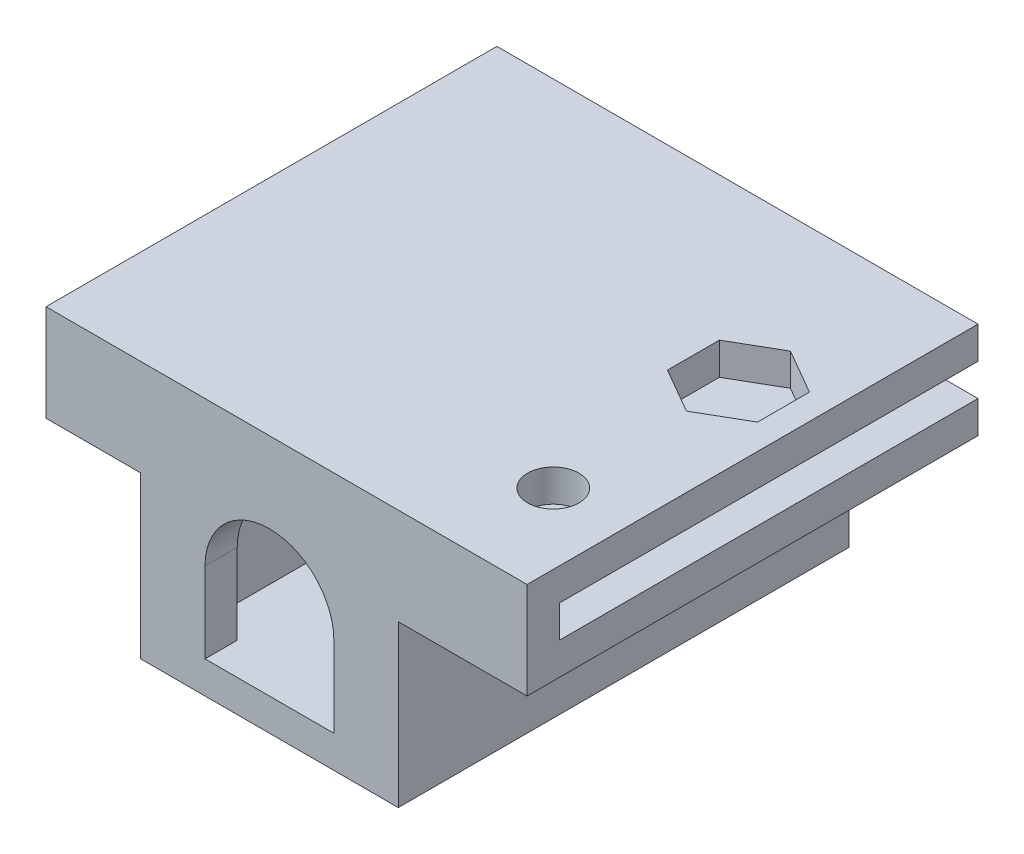
SolidWorks part; units mm, degrees
ref_plane "前视基准面" through (0, 0, 0) normal (0, 0, 1) x (1, 0, 0)
ref_plane "上视基准面" through (0, 0, 0) normal (0, 1, 0) x (1, 0, 0)
ref_plane "右视基准面" through (0, 0, 0) normal (1, 0, 0) x (0, 0, -1)
sketch "草图1" plane through (0, 0, 0) normal (0, 0, 1) x (1, 0, 0)
  line L0 (8, 3) -> (16, 3)
  line L1 (8, -7) -> (-8, -7)
  line L2 (8, -7) -> (8, 3)
  line L3 (8, 5) -> (-8, 5)
  line L4 (6, -4) -> (6, 4)
  line L5 (5, 5) -> (-5, 5)
  line L6 (-6, 4) -> (-6, -4)
  line L7 (-5, -5) -> (5, -5)
  line L8 (6, -4) -> (6, 4)
  line L9 (5, 5) -> (-5, 5)
  line L10 (-6, 4) -> (-6, -4)
  line L11 (-5, -5) -> (5, -5)
  line L12 (88.125, 7) -> (-11.875, 7)
  line L13 (-11.875, 7) -> (-11.875, 5)
  line L14 (-11.875, 5) -> (88.125, 5)
  line L15 (88.125, 5) -> (88.125, 7)
  line L16 (88.125, 7) -> (-11.875, 7)
  line L17 (-11.875, 7) -> (-11.875, 5)
  line L18 (-11.875, 5) -> (88.125, 5)
  line L19 (88.125, 5) -> (88.125, 7)
  line L20 (-8, -7) -> (-8, 3)
  line L21 (-13.875, 3) -> (-8, 3)
  line L22 (-13.875, 3) -> (-13.875, 9)
  line L23 (-13.875, 9) -> (16, 9)
  line L24 (16, 3) -> (16, 9)
  line L26 (4, 0) -> (4, -5)
  line L27 (4, -5) -> (-4, -5)
  line L28 (-4, 0) -> (-4, -5)
  arc A0 (4, 0) -> (-4, 0) centre (0, 0) ccw
  arc A4 (6, 4) -> (5, 5) centre (5, 4) ccw
  arc A5 (-5, 5) -> (-6, 4) centre (-5, 4) ccw
  arc A6 (-6, -4) -> (-5, -5) centre (-5, -4) ccw
  arc A7 (5, -5) -> (6, -4) centre (5, -4) ccw
  arc A8 (6, 4) -> (5, 5) centre (5, 4) ccw
  arc A9 (-5, 5) -> (-6, 4) centre (-5, 4) ccw
  arc A10 (-6, -4) -> (-5, -5) centre (-5, -4) ccw
  arc A11 (5, -5) -> (6, -4) centre (5, -4) ccw
  dimension "D5" = 2
  dimension "D6" = 2
  dimension "D1" = 0
  dimension "D2" = 0
extrude "凸台-拉伸1" add sketch "草图1" along normal blind 2 contours A11 L11 A10 L10 A9 L3 L18 L17 L16 L24 L23 L22 L21 L20 L1 L2 L0 A8 L8 | L18 L24 L16 L17 L3 | L11 A11 L8 A8 L3 A9 L10 A10 L28 A0 L26 region at (7.6611, -2, 0) region at (2.0625, 6, 0) region at (5.5967, 4.5967, 0)
sketch "草图2" plane through (0, 0, 0) normal (0, 0, -1) x (-1, 0, 0)
  line L1 (6, -5) -> (-6, -5)
  line L2 (6, -5) -> (6, 5)
  line L3 (6, 5) -> (-6, 5)
  line L4 (-6, 4) -> (-6, -4)
  line L5 (5, 5) -> (-5, 5)
  line L6 (6, -4) -> (6, 4)
  line L7 (-5, -5) -> (5, -5)
  line L8 (-6, 4) -> (-6, -4)
  line L9 (5, 5) -> (-5, 5)
  line L10 (6, -4) -> (6, 4)
  line L11 (-5, -5) -> (5, -5)
  line L12 (-16, 9) -> (-16, 3)
  line L13 (-16, 3) -> (-8, 3)
  line L14 (-8, 3) -> (-8, -7)
  line L15 (-8, -7) -> (8, -7)
  line L16 (8, -7) -> (8, 3)
  line L17 (8, 3) -> (13.875, 3)
  line L18 (13.875, 3) -> (13.875, 9)
  line L19 (13.875, 9) -> (-16, 9)
  line L23 (11.875, 7) -> (-88.125, 7)
  line L24 (-16, 9) -> (-16, 3)
  line L25 (-16, 3) -> (-8, 3)
  line L26 (-8, 3) -> (-8, -7)
  line L27 (-8, -7) -> (8, -7)
  line L28 (8, -7) -> (8, 3)
  line L29 (8, 3) -> (13.875, 3)
  line L30 (13.875, 3) -> (13.875, 9)
  line L31 (13.875, 9) -> (-16, 9)
  line L36 (-6, -5) -> (-6, 5)
  line L37 (11.875, 5) -> (11.875, 7)
  line L38 (-88.125, 5) -> (11.875, 5)
  line L39 (-88.125, 7) -> (-88.125, 5)
  line L40 (11.875, 7) -> (-88.125, 7)
  line L41 (11.875, 5) -> (11.875, 7)
  line L42 (-88.125, 5) -> (11.875, 5)
  line L43 (-88.125, 7) -> (-88.125, 5)
  arc A4 (-5, 5) -> (-6, 4) centre (-5, 4) ccw
  arc A5 (6, 4) -> (5, 5) centre (5, 4) ccw
  arc A6 (5, -5) -> (6, -4) centre (5, -4) ccw
  arc A7 (-6, -4) -> (-5, -5) centre (-5, -4) ccw
  arc A8 (-5, 5) -> (-6, 4) centre (-5, 4) ccw
  arc A9 (6, 4) -> (5, 5) centre (5, 4) ccw
  arc A10 (5, -5) -> (6, -4) centre (5, -4) ccw
  arc A11 (-6, -4) -> (-5, -5) centre (-5, -4) ccw
  line M21 (4, -5) -> (-4, -5)
  line M25 (-16, 9) -> (-16, 3)
  line M26 (-16, 3) -> (-8, 3)
  line M27 (-8, 3) -> (-8, -7)
  line M28 (-8, -7) -> (8, -7)
  line M29 (8, -7) -> (8, 3)
  line M30 (8, 3) -> (13.875, 3)
  line M31 (13.875, 3) -> (13.875, 9)
  line M32 (13.875, 9) -> (-16, 9)
  line M33 (-16, 9) -> (-16, 3)
  dimension "D1" = 0
  dimension "D2" = 0
  dimension "D3" = 0
extrude "凸台-拉伸2" add sketch "草图2" along normal offset from surface (26 mm away) 2 contours L1 L36 L8 L2 M25 M26 M27 M28 M29 M30 M31 M32 M33 M21 region at (-6.3389, -4.5, 0) offset beyond the face yes
sketch "草图3" plane through (0, 0, -26) normal (0, 0, -1) x (-1, 0, 0)
  line L1 (6, -5) -> (-6, -5)
  line L2 (6, -5) -> (6, -4)
  line L3 (6, -4) -> (-6, -4)
  line L4 (-6, -5) -> (-6, -4)
  line L20 (-16, 5) -> (-16, 3)
  line L21 (-16, 3) -> (-8, 3)
  line L22 (-8, 3) -> (-8, -7)
  line L23 (-8, -7) -> (8, -7)
  line L24 (8, -7) -> (8, 3)
  line L25 (8, 3) -> (13.875, 3)
  line L26 (13.875, 3) -> (13.875, 9)
  line L27 (13.875, 9) -> (-16, 9)
  line L28 (6, 5) -> (6, -5)
  line L29 (6, 5) -> (6, -5)
  line L30 (6, -5) -> (-6, -5)
  line L31 (6, -5) -> (-6, -5)
  line L36 (-16, 5) -> (-16, 3)
  line L37 (-16, 3) -> (-8, 3)
  line L38 (-8, 3) -> (-8, -7)
  line L39 (-8, -7) -> (8, -7)
  line L40 (8, -7) -> (8, 3)
  line L41 (8, 3) -> (13.875, 3)
  line L42 (13.875, 3) -> (13.875, 9)
  line L43 (13.875, 9) -> (-16, 9)
  line L48 (-6, -5) -> (-6, 5)
  line L49 (-6, -5) -> (-6, 5)
  line L50 (-6, 5) -> (-16, 5)
  line L51 (-6, 5) -> (-16, 5)
  line L52 (-16, 9) -> (-16, 7)
  line L53 (-16, 9) -> (-16, 7)
  line L54 (-16, 7) -> (11.875, 7)
  line L55 (-16, 7) -> (11.875, 7)
  line L56 (11.875, 7) -> (11.875, 5)
  line L57 (11.875, 7) -> (11.875, 5)
  line L58 (11.875, 5) -> (6, 5)
  line L59 (11.875, 5) -> (6, 5)
  line M19 (6, 5) -> (6, -5)
  line M20 (6, -5) -> (-6, -5)
  line M21 (-6, -5) -> (-6, 5)
  dimension "D2" = 1
  dimension "D1" = 0
extrude "凸台-拉伸3" add sketch "草图3" against normal blind 1.6 contours L3 M19 M21 M20 region at (0, -4.5, -26)
sketch "草图4" plane through (0, 9, 0) normal (0, 1, 0) x (1, 0, 0)
  line L0 (13.92, 16.825) -> (9.33, 14.175) construction
  line L2 (11.625, 12.2726) -> (14.42, 13.8863)
  line L3 (14.42, 13.8863) -> (14.42, 17.1137)
  line L4 (16, -2) -> (16, 26)
  line L5 (16, 26) -> (-13.875, 26)
  line L6 (-13.875, 26) -> (-13.875, -2)
  line L7 (-13.875, -2) -> (16, -2)
  line L8 (16, -2) -> (16, 26)
  line L9 (16, 26) -> (-13.875, 26)
  line L10 (-13.875, 26) -> (-13.875, -2)
  line L11 (-13.875, -2) -> (16, -2)
  line L12 (14.42, 17.1137) -> (11.625, 18.7274)
  line L13 (11.625, 18.7274) -> (8.83, 17.1137)
  line L14 (11.625, 18.15) -> (9.33, 16.825)
  line L15 (9.33, 16.825) -> (9.33, 14.175)
  line L16 (9.33, 14.175) -> (11.625, 12.85)
  line L17 (11.625, 12.85) -> (13.92, 14.175)
  line L18 (13.92, 14.175) -> (13.92, 16.825)
  line L19 (13.92, 16.825) -> (11.625, 18.15)
  line L20 (11.625, 18.15) -> (9.33, 16.825)
  line L21 (9.33, 16.825) -> (9.33, 14.175)
  line L22 (9.33, 14.175) -> (11.625, 12.85)
  line L23 (11.625, 12.85) -> (13.92, 14.175)
  line L24 (13.92, 14.175) -> (13.92, 16.825)
  line L25 (13.92, 16.825) -> (11.625, 18.15)
  line L26 (8.83, 17.1137) -> (8.83, 13.8863)
  line L27 (8.83, 13.8863) -> (11.625, 12.2726)
  circle A0 centre (11.625, 15.5) radius 2.795 construction
  dimension "D3" = 0.5
  dimension "D1" = 0
  dimension "D2" = 0
extrude "切除-拉伸1" cut sketch "草图4" against normal blind 2 contours L2 L3 L12 L13 L26 L27
sketch "草图5" plane through (0, 3, 0) normal (0, -1, 0) x (1, 0, 0)
  line L0 (11.625, -18.6754) -> (11.625, 2) construction
  line L1 (11.625, -18.6754) -> (14.375, -17.0877)
  line L2 (14.375, -17.0877) -> (14.375, -13.9123)
  line L3 (14.375, -13.9123) -> (11.625, -12.3246)
  line L4 (8, 2) -> (8, -26)
  line L5 (8, -26) -> (16, -26)
  line L6 (16, -26) -> (16, 2)
  line L7 (16, 2) -> (8, 2)
  line L8 (8, 2) -> (8, -26)
  line L9 (8, -26) -> (16, -26)
  line L10 (16, -26) -> (16, 2)
  line L11 (16, 2) -> (8, 2)
  line L12 (11.625, -12.3246) -> (8.875, -13.9123)
  line L13 (8.875, -13.9123) -> (8.875, -17.0877)
  line L14 (8.875, -17.0877) -> (11.625, -18.6754)
  circle A0 centre (11.625, -15.5) radius 1.25 construction
  circle A1 centre (11.625, -15.5) radius 1.25
  circle A2 centre (11.625, -15.5) radius 2.75 construction
  dimension "D2" = 5.5
  dimension "D1" = 0
extrude "切除-拉伸2" cut sketch "草图5" against normal blind 0.5 contours L12 L13 L14 L1 L2 L3
sketch "草图6" plane through (0, 3, 0) normal (0, -1, 0) x (1, 0, 0)
  line L0 (11.625, -18.6754) -> (11.625, 2) construction
  line L1 (14.375, -17.0877) -> (8.875, -13.9123) construction
  line L2 (8.625, -5.7321) -> (11.625, -7.4641)
  line L3 (11.625, -7.4641) -> (14.625, -5.7321)
  line L4 (8, 2) -> (8, -26)
  line L5 (8, -26) -> (16, -26)
  line L6 (16, -26) -> (16, 2)
  line L7 (16, 2) -> (8, 2)
  line L8 (8, 2) -> (8, -26)
  line L9 (8, -26) -> (16, -26)
  line L10 (16, -26) -> (16, 2)
  line L11 (16, 2) -> (8, 2)
  line L12 (14.625, -5.7321) -> (14.625, -2.2679)
  line L13 (14.625, -2.2679) -> (11.625, -0.5359)
  line L14 (14.375, -13.9123) -> (11.625, -12.3246)
  line L15 (11.625, -12.3246) -> (8.875, -13.9123)
  line L16 (8.875, -13.9123) -> (8.875, -17.0877)
  line L17 (8.875, -17.0877) -> (11.625, -18.6754)
  line L18 (11.625, -18.6754) -> (14.375, -17.0877)
  line L19 (14.375, -17.0877) -> (14.375, -13.9123)
  line L20 (14.375, -13.9123) -> (11.625, -12.3246)
  line L21 (11.625, -12.3246) -> (8.875, -13.9123)
  line L22 (8.875, -13.9123) -> (8.875, -17.0877)
  line L23 (8.875, -17.0877) -> (11.625, -18.6754)
  line L24 (11.625, -18.6754) -> (14.375, -17.0877)
  line L25 (14.375, -17.0877) -> (14.375, -13.9123)
  line L26 (11.625, -0.5359) -> (8.625, -2.2679)
  line L27 (8.625, -2.2679) -> (8.625, -5.7321)
  circle A0 centre (11.625, -4) radius 3 construction
  point P6 (11.625, -15.5)
  dimension "D3" = 6
  dimension "D4" = 11.5
  dimension "D1" = 0
  dimension "D2" = 0
extrude "切除-拉伸3" cut sketch "草图6" against normal blind 1 contours L2 L3 L12 L13 L26 L27
sketch "草图7" plane through (0, 4, 0) normal (0, -1, 0) x (1, 0, 0)
  line L0 (8.625, -2.2679) -> (8.625, -5.7321) construction
  line L1 (8.625, -5.7321) -> (11.625, -7.4641) construction
  line L2 (11.625, -7.4641) -> (14.625, -5.7321) construction
  line L3 (14.625, -5.7321) -> (14.625, -2.2679) construction
  line L4 (14.625, -2.2679) -> (11.625, -0.5359) construction
  line L5 (11.625, -0.5359) -> (8.625, -2.2679) construction
  line L6 (14.375, -13.9123) -> (11.625, -12.3246) construction
  line L7 (11.625, -12.3246) -> (8.875, -13.9123) construction
  line L8 (8.875, -13.9123) -> (8.875, -17.0877) construction
  line L9 (8.875, -17.0877) -> (11.625, -18.6754) construction
  line L10 (11.625, -18.6754) -> (14.375, -17.0877) construction
  line L11 (14.375, -17.0877) -> (14.375, -13.9123) construction
  line L12 (8.625, -2.2679) -> (8.625, -5.7321)
  line L13 (8.625, -5.7321) -> (11.625, -7.4641)
  line L14 (11.625, -7.4641) -> (14.625, -5.7321)
  line L15 (14.625, -5.7321) -> (14.625, -2.2679)
  line L16 (14.625, -2.2679) -> (11.625, -0.5359)
  line L17 (11.625, -0.5359) -> (8.625, -2.2679)
  line L18 (14.375, -13.9123) -> (11.625, -12.3246)
  line L19 (11.625, -12.3246) -> (8.875, -13.9123)
  line L20 (8.875, -13.9123) -> (8.875, -17.0877)
  line L21 (8.875, -17.0877) -> (11.625, -18.6754)
  line L22 (11.625, -18.6754) -> (14.375, -17.0877)
  line L23 (14.375, -17.0877) -> (14.375, -13.9123)
  line L24 (11.625, -7.4641) -> (11.625, -0.5359) construction
  circle A0 centre (11.625, -15.5) radius 1.35
  circle A1 centre (11.625, -4) radius 1.6
  dimension "D1" = 3.2
  dimension "D2" = 2.7
extrude "切除-拉伸4" cut sketch "草图7" against normal through all and the other way blind 1 contours A0 | A1
